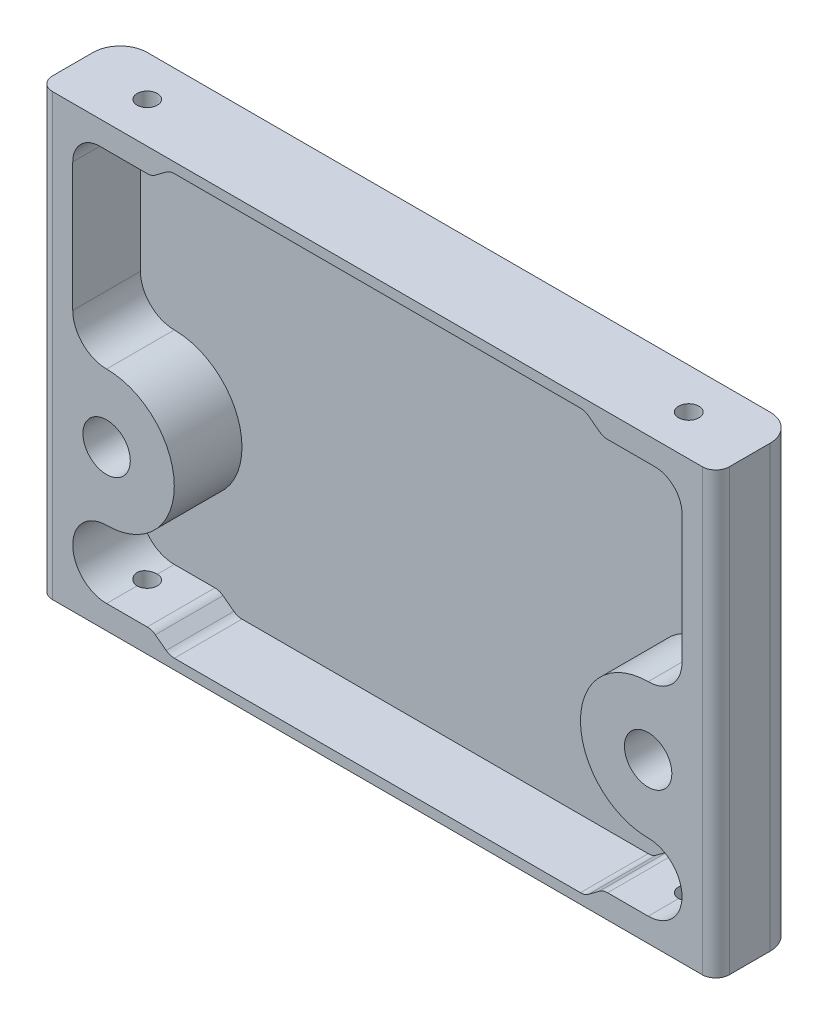
SolidWorks part; units mm, degrees
ref_plane "前视基准面" through (0, 0, 0) normal (0, 0, 1) x (1, 0, 0)
ref_plane "上视基准面" through (0, 0, 0) normal (0, 1, 0) x (1, 0, 0)
ref_plane "右视基准面" through (0, 0, 0) normal (1, 0, 0) x (0, 0, -1)
sketch "草图1" plane through (0, 0, 0) normal (0, 0, 1) x (1, 0, 0)
  line L1 (-50, -32.5) -> (50, -32.5)
  line L2 (-50, -32.5) -> (-50, 32.5)
  line L3 (-50, 32.5) -> (50, 32.5)
  line L4 (50, -32.5) -> (50, 32.5)
  line L5 (-50, -32.5) -> (50, 32.5) construction
  line L6 (-50, 32.5) -> (50, -32.5) construction
  point P0 (0, 0)
  dimension "D1" = 100
  dimension "D2" = 65
extrude "凸台-拉伸1" add sketch "草图1" along normal blind 12
sketch "草图2" plane through (0, 0, 12) normal (0, 0, 1) x (1, 0, 0)
  line L0 (0, 32.5) -> (0, -32.5) construction
  line L1 (50, 32.5) -> (-50, 32.5) construction
  line L2 (-50, -32.5) -> (50, -32.5) construction
  line L3 (30, 31) -> (-30, 31)
  line L4 (-31.2, 30.6) -> (-32.8, 29.4)
  line L5 (-34, 29) -> (-41, 29)
  line L6 (-45, 25) -> (-45, 6)
  line L7 (-40, -29) -> (-34, -29)
  line L8 (-32.8, -29.4) -> (-31.2, -30.6)
  line L9 (-30, -31) -> (30, -31)
  line L10 (-50, 32.5) -> (-50, -32.5) construction
  line L11 (32.8, -29.4) -> (31.2, -30.6)
  line L12 (40, -29) -> (34, -29)
  line L13 (45, 25) -> (45, 6)
  line L14 (34, 29) -> (41, 29)
  line L15 (31.2, 30.6) -> (32.8, 29.4)
  arc A0 (-45, 6) -> (-40, 1) centre (-40, 6) ccw
  arc A1 (-40, 1) -> (-40, -19) centre (-40, -9) cw
  arc A2 (-40, -19) -> (-40, -29) centre (-40, -24) ccw
  arc A3 (-41, 29) -> (-45, 25) centre (-41, 25) ccw
  circle A4 centre (-40, -9) radius 3.5
  circle A5 centre (40, -9) radius 3.5
  arc A6 (41, 29) -> (45, 25) centre (41, 25) cw
  arc A7 (40, -19) -> (40, -29) centre (40, -24) cw
  arc A8 (40, 1) -> (40, -19) centre (40, -9) ccw
  arc A9 (45, 6) -> (40, 1) centre (40, 6) cw
  arc A10 (-34, -29) -> (-32.8, -29.4) centre (-34, -31) cw
  arc A11 (-31.2, -30.6) -> (-30, -31) centre (-30, -29) ccw
  arc A12 (31.2, -30.6) -> (30, -31) centre (30, -29) cw
  arc A13 (32.8, -29.4) -> (34, -29) centre (34, -31) cw
  arc A14 (31.2, 30.6) -> (30, 31) centre (30, 29) ccw
  arc A15 (34, 29) -> (32.8, 29.4) centre (34, 31) cw
  arc A16 (-30, 31) -> (-31.2, 30.6) centre (-30, 29) ccw
  arc A17 (-32.8, 29.4) -> (-34, 29) centre (-34, 31) cw
  point P24 (-45, 29)
  point P25 (-33.3333, -29)
  point P30 (-30.6667, -31)
  point P33 (-45, -24)
  point P46 (0, -31)
  point P49 (0, 31)
  point P50 (30.6667, -31)
  point P53 (33.3333, -29)
  point P56 (30.6667, 31)
  point P59 (33.3333, 29)
  point P62 (-30.6667, 31)
  point P65 (-33.3333, 29)
  dimension "D5" = 4
  dimension "D8" = 7
  dimension "D9" = 10
  dimension "D10" = 23.5
  dimension "D13" = 2
  dimension "D2" = 7
  dimension "D3" = 2
  dimension "D4" = 90
  dimension "D6" = 3.5
  dimension "D7" = 62
  dimension "D11" = 1.5
  dimension "D12" = 60
extrude "切除-拉伸1" cut sketch "草图2" against normal offset from surface (10 mm away) 2 contours L0 L3 L4 L5 A3 L6 A0 A1 A2 L7 L8 L9 | L3 L0 L9 L11 L12 A7 A8 A9 L13 A6 L14 L15 region at (20.3341, 1.0008, 12) region at (-20.3341, 1.0008, 12) up to face at (0, 0, 0)
extrude "切除-拉伸2" cut sketch "草图2<3>" against normal through all contours A5 | A4 region at (40, -9, 12)
sketch "草图2<3>" plane through (0, 0, 12) normal (0, 0, 1) x (1, 0, 0) same geometry as "草图2"
sketch "草图3" plane through (0, 32.5, 0) normal (0, 1, 0) x (1, 0, 0)
  line L0 (50, -12) -> (50, 0) construction
  line L1 (50, -12) -> (-50, -12) construction
  circle A0 centre (40, -6) radius 1.5
  dimension "D1" = 3
  dimension "D2" = 10
  dimension "D3" = 6
extrude "切除-拉伸3" cut sketch "草图3" against normal blind 10
sketch "草图4" plane through (0, -32.5, 0) normal (0, -1, 0) x (1, 0, 0)
  circle A1 centre (40, 6) radius 1.5
  circle A2 centre (40, 6) radius 1.5
  dimension "D1" = 0
extrude "切除-拉伸4" cut sketch "草图4" against normal blind 10
mirror "镜向1" about plane through (0, 0, 0) normal (1, 0, 0) of "切除-拉伸4", "切除-拉伸3"
fillet "圆角2" radius 4 2 edges at (-50, 0, 0) (50, 0, 0)
fillet "圆角3" radius 2 2 edges at (-50, 0, 12) (50, 0, 12)
